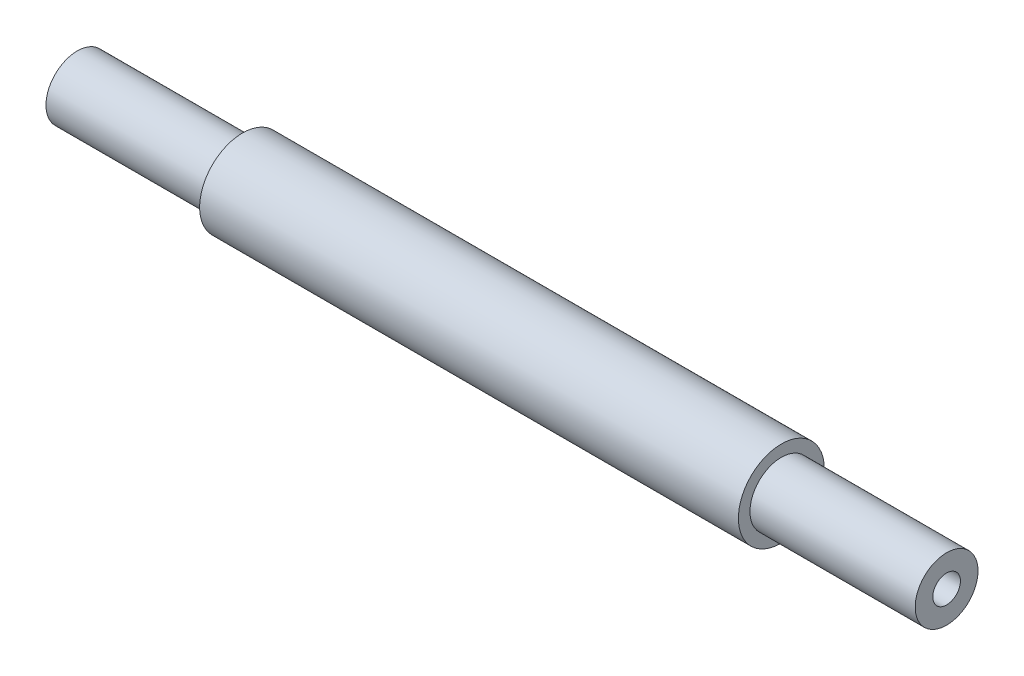
SolidWorks part; units mm, degrees
ref_plane "Front Plane" through (0, 0, 0) normal (0, 0, 1) x (1, 0, 0)
ref_plane "Top Plane" through (0, 0, 0) normal (0, 1, 0) x (1, 0, 0)
ref_plane "Right Plane" through (0, 0, 0) normal (1, 0, 0) x (0, 0, -1)
sketch "Sketch2" plane through (0, 0, 0) normal (1, 0, 0) x (0, 0, -1)
  circle A0 centre (0, 0) radius 0.13
  circle A1 centre (0, 0) radius 0.095
  circle A2 centre (0, 0) radius 0.0418
  dimension "D1" = 0.26
  dimension "D2" = 0.19
extrude "Boss-Extrude1" add sketch "Sketch2" along normal blind 2.63 contours A1 A2 region at (0, 0, 0.0923)
extrude "Boss-Extrude2" add sketch "Sketch2<3>" along normal blind 1.63 from offset 0.5 contours A0 A1 region at (0, 0, 0.1263)
sketch "Sketch2<3>" plane through (0, 0, 0) normal (1, 0, 0) x (0, 0, -1) same geometry as "Sketch2"
